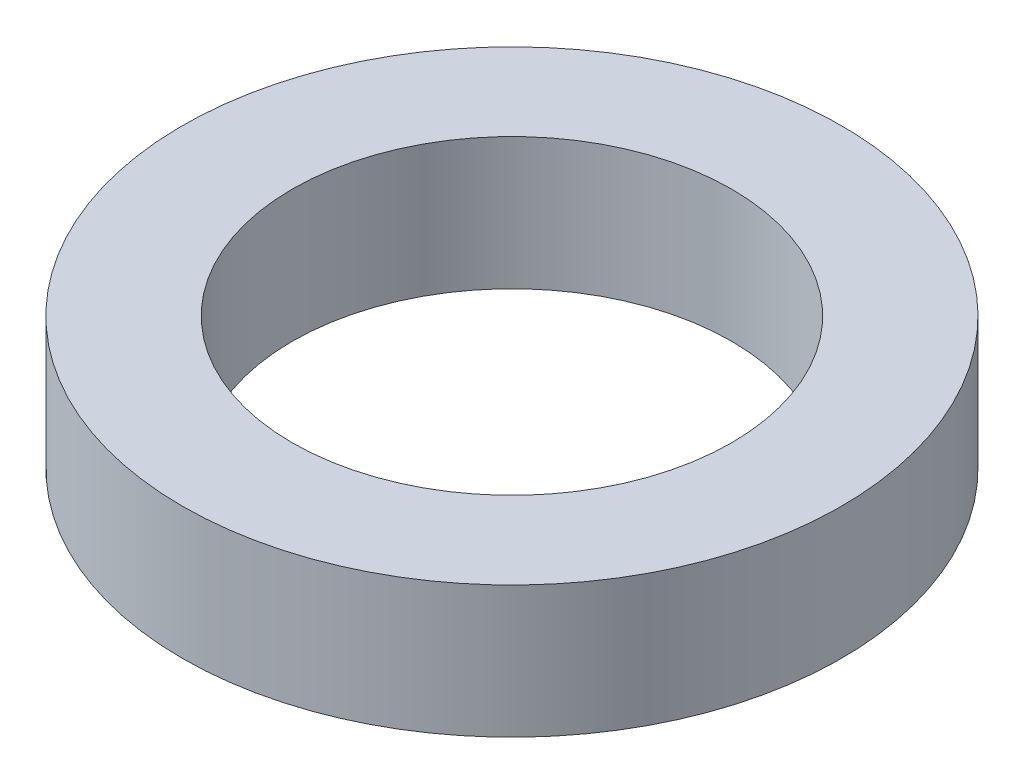
SolidWorks part; units mm, degrees
ref_plane "Front Plane" through (0, 0, 0) normal (0, 0, 1) x (1, 0, 0)
ref_plane "Top Plane" through (0, 0, 0) normal (0, 1, 0) x (1, 0, 0)
ref_plane "Right Plane" through (0, 0, 0) normal (1, 0, 0) x (0, 0, -1)
sketch "Sketch1" plane through (0, 0, 0) normal (0, 1, 0) x (1, 0, 0)
  circle A0 centre (0, 0) radius 45
  dimension "FLANGE_OD" = 90
extrude "Boss-Extrude1" add sketch "Sketch1" along normal blind 18
sketch "Sketch2" plane through (0, 0, 0) normal (0, 1, 0) x (1, 0, 0)
  circle A0 centre (0, 0) radius 30
  dimension "BORE_D" = 60
extrude "Cut-Extrude1" cut sketch "Sketch2" along normal through all
sketch "Sketch3" plane through (0, 18, 0) normal (0, 1, 0) x (1, 0, 0)
  circle A0 centre (0, 0) radius 19.0926 construction
  circle A1 centre (-19.0926, 0) radius 1.5837
  dimension "BOLT_D" = 3.1674
  dimension "BOLT_PCD" = 38.1851
extrude "Cut-Extrude2" cut sketch "Sketch3" against normal blind 16.1263 rebuild error yes
pattern_circular "CirPattern1" count 5 over 360 rebuild error yes
